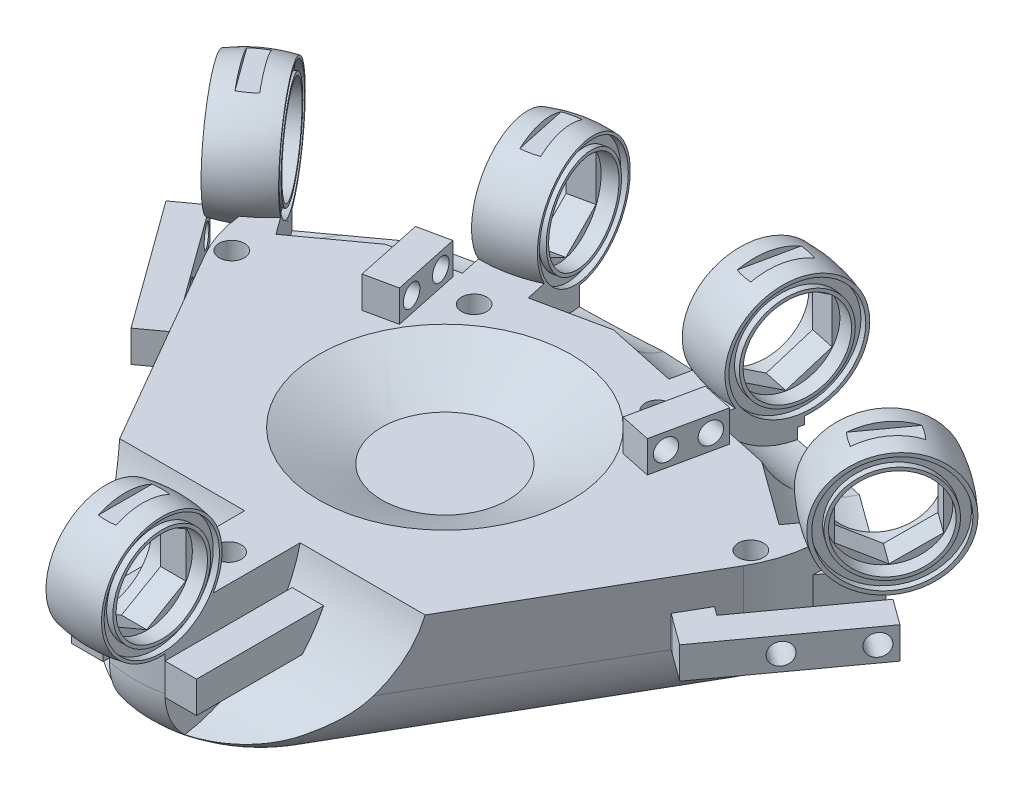
SolidWorks part; units mm, degrees
ref_plane "Front Plane" through (0, 0, 0) normal (0, 0, 1) x (1, 0, 0)
ref_plane "Top Plane" through (0, 0, 0) normal (0, 1, 0) x (1, 0, 0)
ref_plane "Right Plane" through (0, 0, 0) normal (1, 0, 0) x (0, 0, -1)
sketch "Sketch1" plane through (0, 0, 0) normal (0, 1, 0) x (1, 0, 0)
  line L0 (34.641, 0) -> (85.359, 0)
  line L1 (17.3205, -30) -> (42.6795, -73.923)
  line L3 (77.3205, -73.923) -> (102.6795, -30)
  arc A0 (77.3205, -73.923) -> (42.6795, -73.923) centre (60, -63.923) cw
  arc A1 (102.6795, -30) -> (85.359, 0) centre (85.359, -20) ccw
  arc A2 (34.641, 0) -> (17.3205, -30) centre (34.641, -20) ccw
  point P10 (120, 0)
  point P13 (0, 0)
  dimension "D3" = 20
  dimension "D1" = 120
  dimension "D2" = 60
  dimension "D4" = 60
extrude "Boss-Extrude1" add sketch "Sketch1" along normal blind 20
fillet "Fillet1" radius 10 6 edges at (30, 0, 51.9615) (17.3205, 0, 10) (60, 0, 0) (102.6795, 0, 10) (90, 0, 51.9615) (60, 0, 83.923)
ref_plane "Plane1" through (0, 15, 0) normal (0, 1, 0) x (1, 0, 0)
sketch "Sketch2" plane through (0, 20, 0) normal (0, 1, 0) x (1, 0, 0)
  line L0 (17.3205, -10) -> (90, -51.9615) construction
  line L1 (77.3205, -73.923) -> (102.6795, -30) construction
  line L2 (102.6795, -10) -> (30, -51.9615) construction
  line L3 (17.3205, -30) -> (42.6795, -73.923) construction
  circle A0 centre (60, -34.641) radius 20
  arc A1 (34.641, 0) -> (17.3205, -30) centre (34.641, -20) ccw construction
  arc A2 (102.6795, -30) -> (85.359, 0) centre (85.359, -20) ccw construction
sketch "Sketch3" plane through (0, 15, 0) normal (0, 1, 0) x (1, 0, 0)
  line L2 (17.3205, -10) -> (90, -51.9615) construction
  line L3 (77.3205, -73.923) -> (102.6795, -30) construction
  line L4 (102.6795, -10) -> (30, -51.9615) construction
  line L5 (17.3205, -30) -> (42.6795, -73.923) construction
  circle A0 centre (60, -34.641) radius 10
  arc A3 (34.641, 0) -> (17.3205, -30) centre (34.641, -20) ccw construction
  arc A4 (102.6795, -30) -> (85.359, 0) centre (85.359, -20) ccw construction
loft "Cut-Loft1" cut profiles "Sketch3", "Sketch2" connector at (50.0727, 15, 33.4376) connector at (41.9573, 20, 26.0119)
sketch "Sketch4" plane through (0, 20, 0) normal (0, 1, 0) x (1, 0, 0)
  line L0 (60, -83.923) -> (9.8272, -14.8662) construction
  line L2 (77.8384, 0) -> (87.9211, -2.1432) construction
  line L3 (60, -83.923) -> (110.1728, -14.8662) construction
  line L4 (60, -83.923) -> (42.1616, 0) construction
  line L6 (60, -83.923) -> (77.8384, 0) construction
  line L7 (85.359, 0) -> (34.641, 0) construction
  line L9 (42.1616, 0) -> (47.7327, 1.1842) construction
  line L12 (9.8272, -14.8662) -> (15.0082, -11.102) construction
  line L14 (110.1728, -14.8662) -> (114.1984, -17.791) construction
  line L15 (60, -83.923) -> (60, -68.923) construction
  line L16 (60, -83.923) -> (70.4731, -83.923) construction
  line L17 (60, -68.923) -> (60, 1.8749) construction
  arc A2 (42.6795, -73.923) -> (77.3205, -73.923) centre (60, -63.923) ccw construction
  circle A6 centre (60, -83.923) radius 85.7979
  circle A7 centre (60, -83.923) radius 70
  dimension "D4" = 12
  dimension "D1" = 24
  dimension "D2" = 24
  dimension "D3" = 12
ref_plane "Plane3" through (40.3391, 0, -8.5743) normal (0.9781, 0, -0.2079) x (-0.2079, 0, -0.9781)
ref_plane "Plane4" through (74.4737, 0, 15.8299) normal (0.9781, 0, 0.2079) x (0.2079, 0, -0.9781)
ref_plane "Plane5" through (-0.6373, 0, 0.463) normal (0.809, 0, -0.5878) x (-0.5878, 0, -0.809)
ref_plane "Plane6" through (79.1783, 0, 57.5264) normal (0.809, 0, 0.5878) x (0.5878, 0, -0.809)
ref_plane "Plane7" through (30.9945, 0, -42.6602) normal (0.5878, 0, -0.809) x (-0.809, 0, -0.5878)
ref_plane "Plane8" through (10.4645, 0, 14.4032) normal (-0.5878, 0, -0.809) x (-0.809, 0, 0.5878)
ref_plane "Plane9" through (0, 0, 83.923) normal (0, 0, 1) x (1, 0, 0)
ref_plane "Plane14" through (0, 20, 0) normal (0, 1, 0) x (1, 0, 0)
sketch "Sketch5" plane through (22.3094, 0, 5.7974) normal (-0.5878, 0, -0.809) x (-0.809, 0, 0.5878)
  line L0 (15.4287, 46.9474) -> (15.4287, -46.9474) construction
  line L1 (11.0287, 25) -> (19.8287, 25)
  line L2 (18.262, 20) -> (-13.3842, 20) construction
  line L3 (19.8287, 25) -> (19.8287, 34.5394)
  line L4 (11.0287, 25) -> (11.0287, 34.5394)
  ellipse E0 centre (15.4287, 25) end of major axis (30.399, 25) minor radius 9.9802 (19.8287, 34.5394) -> (11.0287, 34.5394) ccw
  dimension "D1" = 5
  dimension "D2" = 4.4
  dimension "D3" = 4.4
revolve "Revolve1" add sketch "Sketch5" angle 360 about L1
ref_plane "Plane10" through (1.8225, 0, 8.5743) normal (-0.2079, 0, -0.9781) x (-0.9781, 0, 0.2079)
ref_plane "Plane11" through (3.3647, 0, -15.8299) normal (0.2079, 0, -0.9781) x (-0.9781, 0, -0.2079)
sketch "Sketch6" plane through (-0.6373, 0, 0.463) normal (0.809, 0, -0.5878) x (-0.5878, 0, -0.809)
  circle A5 centre (-17.8033, 25) radius 7.25
  dimension "D1" = 14.5
extrude "Cut-Extrude1" cut sketch "Sketch6" against normal blind 15 and the other way blind 15
sketch "Sketch12" plane through (2.9224, 0, -2.1233) normal (0.809, 0, -0.5878) x (-0.5878, 0, -0.809)
  circle A0 centre (-17.8033, 25) radius 12.5
  arc A1 (-21.0565, 18.5209) -> (-23.0533, 20) centre (-17.8033, 25) ccw construction
  dimension "D1" = 25
extrude "Cut-Extrude4" cut sketch "Sketch12" along normal blind 15
sketch "Sketch13" plane through (-4.1969, 0, 3.0493) normal (-0.809, 0, 0.5878) x (0.5878, 0, 0.809)
  circle A0 centre (17.8033, 25) radius 7.75
  circle A1 centre (17.8033, 25) radius 9.15
  circle A4 centre (17.8033, 25) radius 7.25 construction
  dimension "D1" = 0.5
  dimension "D2" = 1.4
extrude "Cut-Extrude5" cut sketch "Sketch13" against normal blind 1
sketch "Sketch14" plane through (2.9224, 0, -2.1233) normal (0.809, 0, -0.5878) x (-0.5878, 0, -0.809)
  circle A0 centre (-17.8033, 25) radius 7.75
  circle A1 centre (-17.8033, 25) radius 9.15
  circle A3 centre (-17.8033, 25) radius 7.25 construction
  dimension "D1" = 0.5
  dimension "D2" = 1.4
extrude "Cut-Extrude6" cut sketch "Sketch14" against normal blind 1
ref_plane "Plane13" through (60, 0, 0) normal (1, 0, 0) x (0, 0, -1)
sketch "Sketch17" plane through (1.8225, 0, 8.5743) normal (-0.2079, 0, -0.9781) x (-0.9781, 0, 0.2079)
  line L0 (-41.2403, 46.8697) -> (-41.2403, -46.8697) construction
  line L1 (-45.6403, 25) -> (-36.8403, 25)
  line L2 (93.7395, 20) -> (-93.7395, 20) construction
  line L3 (-45.6403, 25) -> (-45.6403, 34.5601)
  line L4 (-36.8403, 25) -> (-36.8403, 34.5601)
  ellipse E1 centre (-41.2403, 25) end of major axis (-26.2403, 25) minor radius 10 (-36.8403, 34.5601) -> (-45.6403, 34.5601) ccw
  dimension "D1" = 5
  dimension "D2" = 4.4
  dimension "D3" = 4.4
revolve "Revolve3" add sketch "Sketch17" angle 360 about L1
sketch "Sketch18" plane through (36.0352, 0, -7.6595) normal (-0.9781, 0, 0.2079) x (0.2079, 0, 0.9781)
  circle A0 centre (8.7659, 25) radius 7.25
  arc A1 (16.9142, 20) -> (7.8306, 15.4858) centre (8.7659, 25) ccw construction
  dimension "D1" = 14.5
extrude "Cut-Extrude7" cut sketch "Sketch18" against normal blind 10
sketch "Sketch19" plane through (44.6429, 0, -9.4891) normal (0.9781, 0, -0.2079) x (-0.2079, 0, -0.9781)
  circle A0 centre (-8.7659, 25) radius 12.5
  arc A1 (-9.7011, 17.8106) -> (-14.0159, 20) centre (-8.7659, 25) ccw construction
  dimension "D1" = 25
extrude "Cut-Extrude8" cut sketch "Sketch19" along normal blind 15
sketch "Sketch20" plane through (36.0352, 0, -7.6595) normal (-0.9781, 0, 0.2079) x (0.2079, 0, 0.9781)
  circle A0 centre (8.7659, 25) radius 12.5
  arc A1 (16.9142, 20) -> (7.8306, 15.4858) centre (8.7659, 25) ccw construction
  dimension "D1" = 25
extrude "Cut-Extrude9" cut sketch "Sketch20" along normal blind 15
sketch "Sketch21" plane through (3.3647, 0, -15.8299) normal (0.2079, 0, -0.9781) x (-0.9781, 0, -0.2079)
  line L0 (-76.1374, 46.8697) -> (-76.1374, -46.8697) construction
  line L1 (-80.5374, 25) -> (-71.7374, 25)
  line L2 (-76.1374, 20) -> (-86.3817, 20) construction
  line L3 (-80.5374, 25) -> (-80.5374, 34.6779)
  line L4 (-71.7374, 25) -> (-71.7374, 34.6779)
  ellipse E0 centre (-76.1374, 25) end of major axis (-58.6615, 25) minor radius 10 (-71.7374, 34.6779) -> (-80.5374, 34.6779) ccw
  dimension "D1" = 5
  dimension "D2" = 4.4
  dimension "D3" = 4.4
revolve "Revolve4" add sketch "Sketch21" angle 360 about L1
sketch "Sketch22" plane through (74.4737, 0, 15.8299) normal (0.9781, 0, 0.2079) x (0.2079, 0, -0.9781)
  line L0 (16.1835, -5.6694) -> (16.1835, 5.6694) construction
  circle A0 centre (16.1835, 25) radius 7.25
  dimension "D1" = 14.5
extrude "Cut-Extrude10" cut sketch "Sketch22" against normal blind 10 and the other way blind 10
sketch "Sketch23" plane through (78.7775, 0, 16.7447) normal (0.9781, 0, 0.2079) x (0.2079, 0, -0.9781)
  circle A0 centre (16.1835, 25) radius 7.75
  circle A1 centre (16.1835, 25) radius 9.15
  circle A2 centre (16.1835, 25) radius 7.25 construction
  dimension "D1" = 0.5
  dimension "D2" = 1.4
extrude "Cut-Extrude11" cut sketch "Sketch23" against normal blind 1
sketch "Sketch24" plane through (70.1698, 0, 14.9151) normal (-0.9781, 0, -0.2079) x (-0.2079, 0, 0.9781)
  line L0 (-16.1835, 5.6694) -> (-16.1835, -5.6694) construction
  circle A0 centre (-16.1835, 25) radius 9.45
  circle A1 centre (-16.1835, 25) radius 8.05
  circle A2 centre (-16.1835, 25) radius 7.25 construction
  dimension "D1" = 0.8
  dimension "D2" = 1.4
extrude "Cut-Extrude12" cut sketch "Sketch24" against normal blind 1
sketch "Sketch25" plane through (78.7775, 0, 16.7447) normal (0.9781, 0, 0.2079) x (0.2079, 0, -0.9781)
  circle A0 centre (16.1835, 25) radius 12.5
  dimension "D1" = 25
extrude "Cut-Extrude13" cut sketch "Sketch25" along normal blind 15
sketch "Sketch26" plane through (70.1698, 0, 14.9151) normal (-0.9781, 0, -0.2079) x (-0.2079, 0, 0.9781)
  circle A0 centre (-16.1835, 25) radius 12.5
  dimension "D1" = 25
extrude "Cut-Extrude14" cut sketch "Sketch26" along normal blind 15
sketch "Sketch27" plane through (44.6429, 0, -9.4891) normal (0.9781, 0, -0.2079) x (-0.2079, 0, -0.9781)
  line L0 (-8.7659, -3.1326) -> (-8.7659, 3.1326) construction
  circle A0 centre (-8.7659, 25) radius 9.15
  circle A1 centre (-8.7659, 25) radius 7.75
  circle A2 centre (-8.7659, 25) radius 7.25 construction
  dimension "D1" = 0.5
  dimension "D2" = 1.4
extrude "Cut-Extrude15" cut sketch "Sketch27" against normal blind 1
sketch "Sketch28" plane through (36.0352, 0, -7.6595) normal (-0.9781, 0, 0.2079) x (0.2079, 0, 0.9781)
  circle A0 centre (8.7659, 25) radius 9.45
  circle A1 centre (8.7659, 25) radius 8.05
  circle A2 centre (8.7659, 25) radius 7.25 construction
  dimension "D1" = 0.8
  dimension "D2" = 1.4
extrude "Cut-Extrude16" cut sketch "Sketch28" against normal blind 1
sketch "Sketch29" plane through (30.9945, 0, -42.6602) normal (0.5878, 0, -0.809) x (-0.809, 0, -0.5878)
  line L0 (-97.8697, 46.9474) -> (-97.8697, -46.9474) construction
  line L1 (-102.2697, 25) -> (-93.4697, 25)
  line L2 (-102.2697, 25) -> (-102.2697, 34.7266)
  line L3 (-93.4697, 25) -> (-93.4697, 34.7266)
  line L4 (-80.5406, 20) -> (-100.703, 20) construction
  ellipse E0 centre (-97.8697, 25) end of major axis (-78.923, 25) minor radius 10 (-93.4697, 34.7266) -> (-102.2697, 34.7266) ccw
  dimension "D1" = 5
  dimension "D2" = 4.4
  dimension "D3" = 4.4
revolve "Revolve5" add sketch "Sketch29" angle 360 about L1
sketch "Sketch31" plane through (82.738, 0, 60.1127) normal (0.809, 0, 0.5878) x (0.5878, 0, -0.809)
  line L0 (52.7309, -2.7368) -> (52.7309, 2.7368) construction
  circle A1 centre (52.7309, 25) radius 9.15
  circle A2 centre (52.7309, 25) radius 7.75
  dimension "D1" = 15.5
  dimension "D2" = 1.4
extrude "Cut-Extrude17" cut sketch "Sketch31" against normal blind 1
sketch "Sketch32" plane through (79.1783, 0, 57.5264) normal (0.809, 0, 0.5878) x (0.5878, 0, -0.809)
  circle A1 centre (52.7309, 25) radius 7.25
  dimension "D1" = 14.5
extrude "Cut-Extrude18" cut sketch "Sketch32" against normal blind 10 and the other way blind 10
sketch "Sketch33" plane through (75.6186, 0, 54.9401) normal (-0.809, 0, -0.5878) x (-0.5878, 0, 0.809)
  line L0 (-52.7309, 2.7368) -> (-52.7309, -2.7368) construction
  circle A0 centre (-52.7309, 25) radius 9.15
  circle A1 centre (-52.7309, 25) radius 7.75
  circle A2 centre (-52.7309, 25) radius 7.25 construction
  dimension "D1" = 0.5
  dimension "D2" = 1.4
extrude "Cut-Extrude19" cut sketch "Sketch33" against normal blind 1
sketch "Sketch34" plane through (0, 0, 83.923) normal (0, 0, 1) x (1, 0, 0)
  line L0 (60, -42.8798) -> (60, 42.8798) construction
  line L1 (55.6, 25) -> (64.4, 25)
  line L2 (55.6, 25) -> (55.6, 34.5601)
  line L3 (64.4, 25) -> (64.4, 34.5601)
  line L4 (60, 20) -> (70.4731, 20) construction
  ellipse E0 centre (60, 25) end of major axis (75, 25) minor radius 10 (64.4, 34.5601) -> (55.6, 34.5601) ccw
  dimension "D1" = 5
  dimension "D2" = 4.4
  dimension "D3" = 4.4
revolve "Revolve6" add sketch "Sketch34" angle 360 about L1
sketch "Sketch36" plane through (75.6186, 0, 54.9401) normal (-0.809, 0, -0.5878) x (-0.5878, 0, 0.809)
  circle A0 centre (-52.7309, 25) radius 12.5
  dimension "D1" = 25
extrude "Cut-Extrude21" cut sketch "Sketch36" along normal blind 15
sketch "Sketch37" plane through (60, 0, 0) normal (1, 0, 0) x (0, 0, -1)
  line L0 (-83.923, 42.77) -> (-83.923, -42.77) construction
  circle A0 centre (-83.923, 25) radius 7.25
  dimension "D1" = 14.5
extrude "Cut-Extrude22" cut sketch "Sketch37" against normal blind 10 and the other way blind 10
sketch "Sketch38" plane through (64.4, 0, 0) normal (1, 0, 0) x (0, 0, -1)
  circle A0 centre (-83.923, 25) radius 7.75
  circle A1 centre (-83.923, 25) radius 9.15
  circle A2 centre (-83.923, 25) radius 7.25 construction
  dimension "D1" = 0.5
  dimension "D2" = 1.4
extrude "Cut-Extrude23" cut sketch "Sketch38" against normal blind 1
sketch "Sketch39" plane through (55.6, 0, 0) normal (-1, 0, 0) x (0, 0, 1)
  circle A0 centre (83.923, 25) radius 8.05
  circle A1 centre (83.923, 25) radius 9.45
  circle A2 centre (83.923, 25) radius 7.25 construction
  dimension "D1" = 0.8
  dimension "D2" = 1.4
extrude "Cut-Extrude24" cut sketch "Sketch39" against normal blind 1
sketch "Sketch40" plane through (55.6, 0, 0) normal (-1, 0, 0) x (0, 0, 1)
  circle A0 centre (83.923, 25) radius 22.5
  dimension "D1" = 45
extrude "Cut-Extrude25" cut sketch "Sketch40" along normal blind 20
sketch "Sketch44" plane through (0, 20, 0) normal (0, 1, 0) x (1, 0, 0)
  line L0 (60, -83.923) -> (9.8272, -14.8662) construction
  line L1 (60, -83.923) -> (42.1616, 0) construction
  line L2 (60, -83.923) -> (77.8384, 0) construction
  line L3 (60, -83.923) -> (110.1728, -14.8662) construction
  circle A0 centre (18.855, -27.2919) radius 2
  circle A1 centre (60, -83.923) radius 70 construction
  circle A2 centre (45.4462, -15.4527) radius 2
  circle A3 centre (74.5538, -15.4527) radius 2
  circle A4 centre (101.145, -27.2919) radius 2
  circle A5 centre (60, -68.923) radius 2
extrude "Cut-Extrude27" cut sketch "Sketch44" against normal blind 20
sketch "Sketch47" plane through (10.4645, 0, 14.4032) normal (-0.5878, 0, -0.809) x (-0.809, 0, 0.5878)
  line L2 (5.2877, 14.1016) -> (5.2877, -1.8)
  line L3 (5.2877, -1.8) -> (-27.6426, -1.8)
  line L4 (-27.6426, 14.1016) -> (-27.6426, -1.8)
  line L5 (-27.6426, 14.1016) -> (5.2877, 14.1016)
extrude "Cut-Extrude28" cut sketch "Sketch47" along normal blind 10
sketch "Sketch48" plane through (30.9945, 0, -42.6602) normal (0.5878, 0, -0.809) x (-0.809, 0, -0.5878)
  line L1 (-107.1174, 14.5) -> (-65.8644, 14.5)
  line L2 (-107.1174, 14.5) -> (-107.1174, -2.7463)
  line L3 (-107.1174, -2.7463) -> (-65.8644, -2.7463)
  line L4 (-65.8644, 14.5) -> (-65.8644, -2.7463)
extrude "Cut-Extrude29" cut sketch "Sketch48" along normal blind 10
sketch "Sketch49" plane through (3.3647, 0, -15.8299) normal (0.2079, 0, -0.9781) x (-0.9781, 0, -0.2079)
  line L1 (-95.8088, 14.1838) -> (-62.3691, 14.1838)
  line L2 (-95.8088, 14.1838) -> (-95.8088, -4.9505)
  line L3 (-95.8088, -4.9505) -> (-62.3691, -4.9505)
  line L4 (-62.3691, 14.1838) -> (-62.3691, -4.9505)
extrude "Cut-Extrude30" cut sketch "Sketch49" along normal blind 10
sketch "Sketch50" plane through (1.8225, 0, 8.5743) normal (-0.2079, 0, -0.9781) x (-0.9781, 0, 0.2079)
  line L1 (-49.212, 14.5564) -> (-20.6415, 14.5564)
  line L2 (-49.212, 14.5564) -> (-49.212, -10.5124)
  line L3 (-49.212, -10.5124) -> (-20.6415, -10.5124)
  line L4 (-20.6415, 14.5564) -> (-20.6415, -10.5124)
extrude "Cut-Extrude31" cut sketch "Sketch50" along normal blind 10
sketch "Sketch51" plane through (10.4645, 0, 14.4032) normal (-0.5878, 0, -0.809) x (-0.809, 0, 0.5878)
  line L0 (-9.2789, 10) -> (3.621, 10) construction
  line L1 (-18.4351, 12.5) -> (-3.4351, 12.5)
  line L2 (-18.4351, 12.5) -> (-18.4351, 10)
  line L3 (-18.4351, 10) -> (-3.4351, 10)
  line L4 (-3.4351, 12.5) -> (-3.4351, 10)
  dimension "D1" = 15
extrude "Boss-Extrude2" add sketch "Sketch51" against normal blind 40
sketch "Sketch56" plane through (30.9945, 0, -42.6602) normal (0.5878, 0, -0.809) x (-0.809, 0, -0.5878)
  line L0 (-102.2697, 34.7266) -> (-102.2697, 15.2734) construction
  line L1 (-102.7697, 15) -> (-107.7697, 15)
  line L2 (-102.7697, 15) -> (-102.7697, 10)
  line L3 (-102.7697, 10) -> (-107.7697, 10)
  line L4 (-107.7697, 15) -> (-107.7697, 10)
  line L5 (-106.0045, 20) -> (-100.703, 20) construction
  dimension "D1" = 5
  dimension "D2" = 5
  dimension "D3" = 0.5
  dimension "D4" = 5
extrude "Boss-Extrude6" add sketch "Sketch56" against normal blind 25 separate body
sketch "Sketch57" plane through (83.1425, 0, 60.4065) normal (-0.809, 0, -0.5878) x (-0.5878, 0, 0.809)
  line L1 (-32.7456, 15) -> (-27.7456, 15)
  line L2 (-32.7456, 15) -> (-32.7456, 10)
  line L3 (-32.7456, 10) -> (-27.7456, 10)
  line L4 (-27.7456, 15) -> (-27.7456, 10)
  dimension "D1" = 5
extrude "Boss-Extrude7" add sketch "Sketch57" along normal blind 5
sketch "Sketch59" plane through (87.1876, 0, 63.3455) normal (0.809, 0, 0.5878) x (0.5878, 0, -0.809)
  line L0 (52.7309, 15) -> (52.7309, 10) construction
  line L1 (27.7309, 15) -> (52.7309, 15) construction
  line L2 (27.7309, 10) -> (52.7309, 10) construction
  circle A0 centre (50.2309, 12.5) radius 1.7
  circle A1 centre (39.2309, 12.5) radius 1.7
  dimension "D5" = 11
  dimension "D4" = 3.4
  dimension "D6" = 3.4
  dimension "D1" = 2.5
  dimension "D2" = 2.5
  dimension "D3" = 2.5
extrude "Cut-Extrude33" cut sketch "Sketch59" against normal blind 5 contours A1 | A0
sketch "Sketch62" plane through (60, 0, 0) normal (1, 0, 0) x (0, 0, -1)
  line L1 (-83.923, 17.8409) -> (-77.723, 21.4204)
  line L2 (-77.723, 21.4204) -> (-77.723, 28.5796)
  line L3 (-77.723, 28.5796) -> (-83.923, 32.1591)
  line L4 (-83.923, 32.1591) -> (-90.123, 28.5796)
  line L5 (-90.123, 28.5796) -> (-90.123, 21.4204)
  line L6 (-90.123, 21.4204) -> (-83.923, 17.8409)
  circle A0 centre (-83.923, 25) radius 6.2 construction
  circle A1 centre (-83.923, 25) radius 7.25
  arc A2 (-78.673, 20) -> (-83.433, 17.7666) centre (-83.923, 25) ccw construction
  dimension "D1" = 12.4
extrude "Boss-Extrude10" add sketch "Sketch62" along normal blind 2 and the other way blind 2 contours L3 A1 | L2 A1 | L1 A1 | L6 A1 | L5 A1 | L4 A1 region at (60, 25, 90.968)
sketch "Sketch63" plane through (40.3391, 0, -8.5743) normal (0.9781, 0, -0.2079) x (-0.2079, 0, -0.9781)
  line L1 (-8.7659, 17.8409) -> (-2.5659, 21.4204)
  line L2 (-2.5659, 21.4204) -> (-2.5659, 28.5796)
  line L3 (-2.5659, 28.5796) -> (-8.7659, 32.1591)
  line L4 (-8.7659, 32.1591) -> (-14.9659, 28.5796)
  line L5 (-14.9659, 28.5796) -> (-14.9659, 21.4204)
  line L6 (-14.9659, 21.4204) -> (-8.7659, 17.8409)
  circle A0 centre (-8.7659, 25) radius 6.2 construction
  circle A2 centre (-8.7659, 25) radius 7.25
  circle A3 centre (-8.7659, 25) radius 7.25 construction
  dimension "D1" = 12.4
extrude "Boss-Extrude11" add sketch "Sketch63" along normal blind 2 and the other way blind 2 contours L2 A2 | L3 A2 | L4 A2 | L5 A2 | L6 A2 | L1 A2 region at (43.6263, 25, 6.891)
sketch "Sketch64" plane through (-0.6373, 0, 0.463) normal (0.809, 0, -0.5878) x (-0.5878, 0, -0.809)
  line L1 (-17.8033, 17.8409) -> (-11.6033, 21.4204)
  line L2 (-11.6033, 21.4204) -> (-11.6033, 28.5796)
  line L3 (-11.6033, 28.5796) -> (-17.8033, 32.1591)
  line L4 (-17.8033, 32.1591) -> (-24.0033, 28.5796)
  line L5 (-24.0033, 28.5796) -> (-24.0033, 21.4204)
  line L6 (-24.0033, 21.4204) -> (-17.8033, 17.8409)
  circle A0 centre (-17.8033, 25) radius 6.2 construction
  circle A1 centre (-17.8033, 25) radius 7.25
  circle A2 centre (-17.8033, 25) radius 7.25 construction
  dimension "D1" = 12.4
extrude "Boss-Extrude12" add sketch "Sketch64" along normal blind 2 and the other way blind 2 contours L2 A1 | L3 A1 | L4 A1 | L5 A1 | L6 A1 | L1 A1 region at (13.9682, 25, 20.5657)
sketch "Sketch41" plane through (64.4, 0, 0) normal (1, 0, 0) x (0, 0, -1)
  circle A0 centre (-83.923, 25) radius 22.5
  dimension "D1" = 45
extrude "Cut-Extrude26" cut sketch "Sketch41" along normal blind 20
sketch "Sketch60" plane through (0, 0, 83.923) normal (0, 0, 1) x (1, 0, 0)
  line L0 (55.6, 10) -> (55.6, 15.4525) construction
  line L1 (50.1, 15) -> (55.1, 15)
  line L2 (50.1, 15) -> (50.1, 10)
  line L3 (50.1, 10) -> (55.1, 10)
  line L4 (55.1, 15) -> (55.1, 10)
  line L5 (55.6, 10) -> (64.4, 10) construction
  dimension "D1" = 0.5
  dimension "D2" = 0
  dimension "D3" = 5
  dimension "D4" = 5
extrude "Boss-Extrude9" add sketch "Sketch60" against normal blind 25
sketch "Sketch65" plane through (50.1, 0, 0) normal (-1, 0, 0) x (0, 0, 1)
  line L0 (83.923, 15) -> (83.923, 10) construction
  line L1 (63.7674, 15) -> (83.923, 15) construction
  circle A0 centre (81.423, 12.5) radius 1.5
  circle A1 centre (70.423, 12.5) radius 1.5
  dimension "D5" = 3
  dimension "D6" = 3
  dimension "D1" = 2.5
  dimension "D2" = 2.5
  dimension "D3" = 11
  dimension "D4" = 2.5
extrude "Cut-Extrude35" cut sketch "Sketch65" against normal blind 5
sketch "Sketch66" plane through (0, 20, 0) normal (0, 1, 0) x (1, 0, 0)
  line L0 (39.9939, -13.3693) -> (35.1031, -14.4088)
  line L1 (35.1031, -14.4088) -> (37.3902, -25.1685)
  line L2 (37.3902, -25.1685) -> (42.2809, -24.1289)
  line L3 (42.2809, -24.1289) -> (39.9939, -13.3693)
  line L4 (40.2397, -12.1209) -> (39.5519, -8.8851) construction
  line L5 (30.1427, -14.2671) -> (40.2397, -12.1209) construction
  dimension "D1" = 0.5
  dimension "D2" = 5
  dimension "D3" = 11
  dimension "D4" = 1.17
extrude "Boss-Extrude13" add sketch "Sketch66" along normal blind 5
sketch "Sketch67" plane through (35.5462, 0, -7.5556) normal (0.9781, 0, -0.2079) x (-0.2079, 0, -0.9781)
  line L0 (-32.3923, 25) -> (-21.3923, 25) construction
  line L1 (-21.3923, 25) -> (-21.3923, 20) construction
  line L2 (-32.3923, 25) -> (-32.3923, 20) construction
  circle A0 centre (-29.8923, 22.5) radius 1.7
  circle A1 centre (-23.8923, 22.5) radius 1.7
  dimension "D1" = 3.4
  dimension "D2" = 3.4
  dimension "D3" = 2.5
  dimension "D4" = 2.5
  dimension "D5" = 2.5
  dimension "D6" = 2.5
extrude "Cut-Extrude36" cut sketch "Sketch67" against normal blind 5
sketch "Sketch61" plane through (0, 0, 0) normal (0, -1, 0) x (1, 0, 0)
  circle A0 centre (60, 34.641) radius 20 construction
  circle A1 centre (60, 54.641) radius 1.5
  circle A2 centre (80, 34.641) radius 1.5
  circle A3 centre (60, 14.641) radius 1.5
  circle A4 centre (40, 34.641) radius 1.5
  dimension "D1" = 3
  dimension "D2" = 3
  dimension "D3" = 3
  dimension "D4" = 3
extrude "Cut-Extrude34" cut sketch "Sketch61" against normal blind 10
sketch "Sketch70" plane through (30.9945, 0, -42.6602) normal (0.5878, 0, -0.809) x (-0.809, 0, -0.5878)
  line L0 (-100.703, 10) -> (-87.8031, 10) construction
  line L2 (-93.4697, 15.2734) -> (-93.4697, 10)
  line L3 (-93.4697, 10) -> (-97.8667, 10)
  line L4 (-97.8667, 15.2734) -> (-97.8667, 10)
  line L10 (-93.4697, 15.2734) -> (-93.4697, 15.85)
  line L11 (-93.4697, 15.2734) -> (-93.4697, 34.7266) construction
  line L12 (-93.4697, 15.85) -> (-97.8667, 15.85)
  line L13 (-97.8667, 15.85) -> (-97.8667, 15.2734)
extrude "Boss-Extrude15" add sketch "Sketch70" against normal blind 10
mirror "Mirror5" about plane through (60, 0, 0) normal (1, 0, 0) of "Cut-Extrude36", "Boss-Extrude13", "Boss-Extrude9", "Boss-Extrude15"
sketch "Sketch71" plane through (10.4645, 0, 14.4032) normal (-0.5878, 0, -0.809) x (-0.809, 0, 0.5878)
  line L0 (5.1877, 15.4606) -> (5.1877, 34.5394) construction
  line L1 (5.6877, 15) -> (10.6877, 15)
  line L2 (5.6877, 15) -> (5.6877, 10)
  line L3 (5.6877, 10) -> (10.6877, 10)
  line L4 (10.6877, 15) -> (10.6877, 10)
  line L5 (3.621, 20) -> (7.4816, 20) construction
  dimension "D1" = 5
  dimension "D2" = 5
  dimension "D3" = 0.5
  dimension "D4" = 5
extrude "Boss-Extrude16" add sketch "Sketch71" against normal blind 25 separate body
sketch "Sketch72" plane through (-4.6015, 0, 3.3432) normal (0.809, 0, -0.5878) x (-0.5878, 0, -0.809)
  line L1 (-42.8033, 15) -> (-37.8033, 15)
  line L2 (-42.8033, 15) -> (-42.8033, 10)
  line L3 (-42.8033, 10) -> (-37.8033, 10)
  line L4 (-37.8033, 15) -> (-37.8033, 10)
  dimension "D1" = 5
  dimension "D2" = 5
extrude "Boss-Extrude17" add sketch "Sketch72" along normal blind 5
sketch "Sketch73" plane through (-8.6465, 0, 6.2821) normal (-0.809, 0, 0.5878) x (0.5878, 0, 0.809)
  line L0 (17.8033, 10) -> (17.8033, 15) construction
  line L1 (42.8033, 10) -> (17.8033, 10) construction
  circle A0 centre (20.3033, 12.5) radius 1.7
  circle A1 centre (31.3033, 12.5) radius 1.7
  dimension "D1" = 3.4
  dimension "D5" = 3.4
  dimension "D2" = 2.5
  dimension "D3" = 2.5
  dimension "D4" = 2.5
  dimension "D6" = 11
extrude "Cut-Extrude37" cut sketch "Sketch73" against normal blind 5
sketch "Sketch74" plane through (79.1783, 0, 57.5264) normal (0.809, 0, 0.5878) x (0.5878, 0, -0.809)
  line L1 (52.7309, 32.1591) -> (46.5309, 28.5796)
  line L2 (46.5309, 28.5796) -> (46.5309, 21.4204)
  line L3 (46.5309, 21.4204) -> (52.7309, 17.8409)
  line L4 (52.7309, 17.8409) -> (58.9309, 21.4204)
  line L5 (58.9309, 21.4204) -> (58.9309, 28.5796)
  line L6 (58.9309, 28.5796) -> (52.7309, 32.1591)
  circle A0 centre (52.7309, 25) radius 7.25
  circle A1 centre (52.7309, 25) radius 6.2 construction
  dimension "D1" = 12.4
extrude "Boss-Extrude18" add sketch "Sketch74" along normal blind 2 and the other way blind 2
sketch "Sketch75" plane through (74.4737, 0, 15.8299) normal (0.9781, 0, 0.2079) x (0.2079, 0, -0.9781)
  line L1 (16.1835, 17.8409) -> (22.3835, 21.4204)
  line L2 (22.3835, 21.4204) -> (22.3835, 28.5796)
  line L3 (22.3835, 28.5796) -> (16.1835, 32.1591)
  line L4 (16.1835, 32.1591) -> (9.9835, 28.5796)
  line L5 (9.9835, 28.5796) -> (9.9835, 21.4204)
  line L6 (9.9835, 21.4204) -> (16.1835, 17.8409)
  circle A0 centre (16.1835, 25) radius 7.25
  circle A1 centre (16.1835, 25) radius 6.2 construction
  dimension "D1" = 12.4
extrude "Boss-Extrude19" add sketch "Sketch75" along normal blind 2 and the other way blind 2
ref_plane "Plane15" through (0, 35, 0) normal (0, 1, 0) x (1, 0, 0)
sketch "Sketch77" plane through (0, 35, 0) normal (0, 1, 0) x (1, 0, 0)
  line L0 (64.4, -93.4832) -> (64.4, -74.3629) construction
  line L1 (58.6, -78.923) -> (61.4, -78.923)
  line L2 (58.6, -78.923) -> (58.6, -88.923)
  line L3 (58.6, -88.923) -> (61.4, -88.923)
  line L4 (61.4, -78.923) -> (61.4, -88.923)
  line L5 (55.6, -74.3629) -> (55.6, -93.4832) construction
  line L6 (64.9, -83.923) -> (69.9, -83.923) construction
  line L7 (75.4294, -4.5997) -> (77.5085, 5.1818)
  line L8 (75.4294, -4.5997) -> (78.1682, -5.1818)
  line L9 (77.5085, 5.1818) -> (80.2474, 4.5997)
  line L10 (78.1682, -5.1818) -> (80.2474, 4.5997)
  line L11 (75.4294, -4.5997) -> (80.2474, 4.5997) construction
  line L12 (77.5085, 5.1818) -> (78.1682, -5.1818) construction
  line L14 (39.7526, 4.5997) -> (42.4915, 5.1818)
  line L15 (39.7526, 4.5997) -> (41.8318, -5.1818)
  line L16 (41.8318, -5.1818) -> (44.5706, -4.5997)
  line L17 (42.4915, 5.1818) -> (44.5706, -4.5997)
  line L18 (114.2443, -11.644) -> (111.9791, -9.9982)
  line L19 (114.2443, -11.644) -> (108.3664, -19.7342)
  line L20 (108.3664, -19.7342) -> (106.1012, -18.0884)
  line L21 (111.9791, -9.9982) -> (106.1012, -18.0884)
  line L22 (5.7557, -11.644) -> (8.0209, -9.9982)
  line L23 (5.7557, -11.644) -> (11.6336, -19.7342)
  line L24 (11.6336, -19.7342) -> (13.8988, -18.0884)
  line L25 (8.0209, -9.9982) -> (13.8988, -18.0884)
  line L27 (0.6605, -9.7349) -> (11.8747, -25.17) construction
  line L28 (18.994, -19.9975) -> (7.7798, -4.5624) construction
  line L29 (7.6016, -16.4832) -> (24.9575, -3.8734) construction
  line L30 (35.8701, 8.4364) -> (39.8454, -10.266) construction
  line L31 (48.4531, -8.4364) -> (44.4778, 10.266) construction
  line L32 (75.5467, 10.3812) -> (71.5224, -8.5516) construction
  line L33 (112.3302, -4.4109) -> (100.8959, -20.1489) construction
  line L34 (108.0153, -25.3214) -> (119.4496, -9.5834) construction
  line L35 (114.1369, -17.7463) -> (118.182, -20.6853) construction
  line L36 (80.1301, -10.3812) -> (84.1544, 8.5516) construction
  line L37 (75.0419, 8.0064) -> (72.0272, -6.1768) construction
  line L38 (94.6212, -3.5673) -> (82.1422, -0.9148) construction
  line L39 (47.9728, -6.1768) -> (44.9581, 8.0064) construction
  line L40 (37.8578, -0.9148) -> (25.3788, -3.5673) construction
  line L41 (17.6484, -18.1453) -> (9.1255, -6.4146) construction
  line L42 (13.3869, -12.2799) -> (17.9713, -8.9492) construction
  point P11 (77.8384, 0)
  dimension "D1" = 3
  dimension "D2" = 3
  dimension "D3" = 10
  dimension "D4" = 5
  dimension "D5" = 3
  dimension "D6" = 3
  dimension "D7" = 10
  dimension "D8" = 5
  dimension "D9" = 3
  dimension "D10" = 3
  dimension "D11" = 10
  dimension "D12" = 5
  dimension "D13" = 3
  dimension "D14" = 3
  dimension "D15" = 10
  dimension "D16" = 5
  dimension "D17" = 10
  dimension "D18" = 3
  dimension "D19" = 3
  dimension "D20" = 5
extrude "Cut-Extrude38" cut sketch "Sketch77" against normal blind 1
